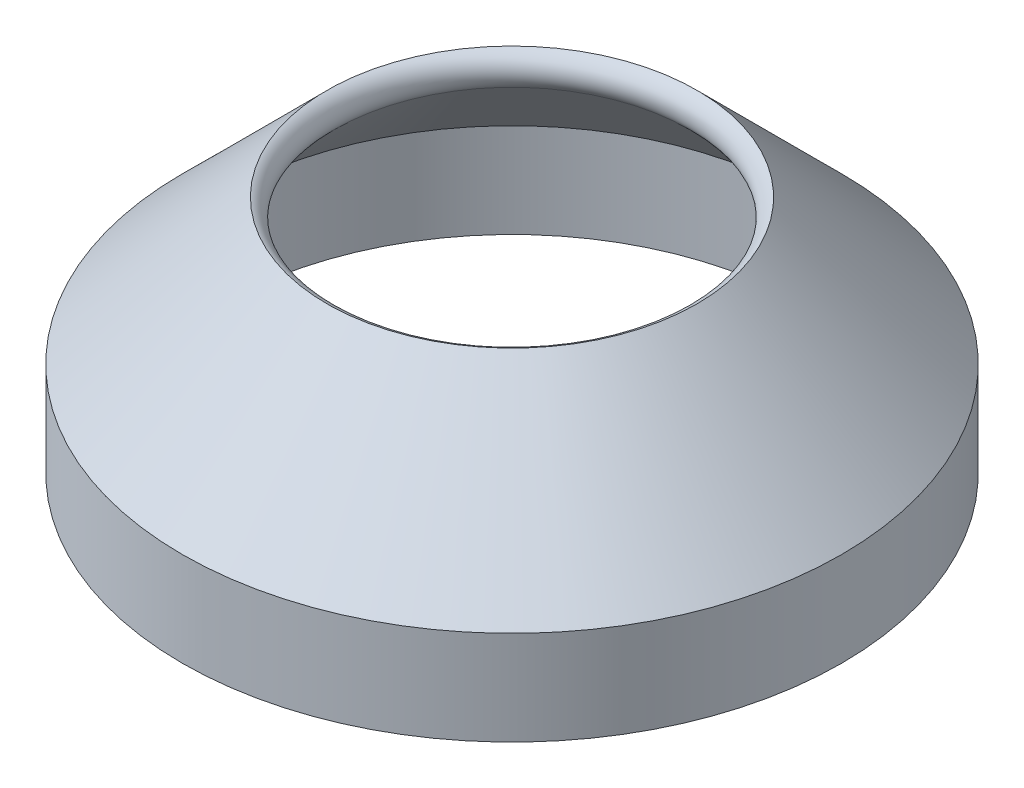
SolidWorks part; units mm, degrees
ref_plane "Front Plane" through (0, 0, 0) normal (0, 0, 1) x (1, 0, 0)
ref_plane "Top Plane" through (0, 0, 0) normal (0, 1, 0) x (1, 0, 0)
ref_plane "Right Plane" through (0, 0, 0) normal (1, 0, 0) x (0, 0, -1)
sketch "Sketch2" plane through (0, 0, 0) normal (0, 0, 1) x (1, 0, 0)
  line L0 (-31, 0) -> (-31, 10)
  line L1 (-31, 10) -> (-15.6394, 25.3606)
  line L2 (-15.6394, 25.3606) -> (-19.6394, 25.3606)
  line L3 (-19.6394, 25.3606) -> (-35, 10)
  line L4 (-35, 10) -> (-35, 0)
  line L5 (-35, 0) -> (-31, 0)
  line L6 (-31, 0) -> (0, 0) construction
  line L7 (0, 0) -> (0, 25.3606) construction
  line L8 (0, 25.3606) -> (-15.6394, 25.3606) construction
  dimension "D1" = 135
  dimension "D2" = 4
  dimension "D3" = 4
  dimension "D4" = 31
  dimension "D5" = 10
revolve "Revolve1" add sketch "Sketch2" angle 360 about L7
fillet "Fillet1" radius 2 1 edges at (15.6394, 25.3606, 0)
sketch "Sketch3" plane through (0, 0, 0) normal (0, -1, 0) x (1, 0, 0)
  circle A0 centre (0, 33) radius 1.15
  circle A1 centre (0, 0) radius 35 construction
  dimension "D1" = 2.3
  dimension "D2" = 33
extrude "Cut-Extrude1" cut sketch "Sketch3" against normal blind 10
pattern_circular "CirPattern1" count 4 over 360 about axis through (0, 0, 0) along (0, -1, 0) of "Cut-Extrude1"
